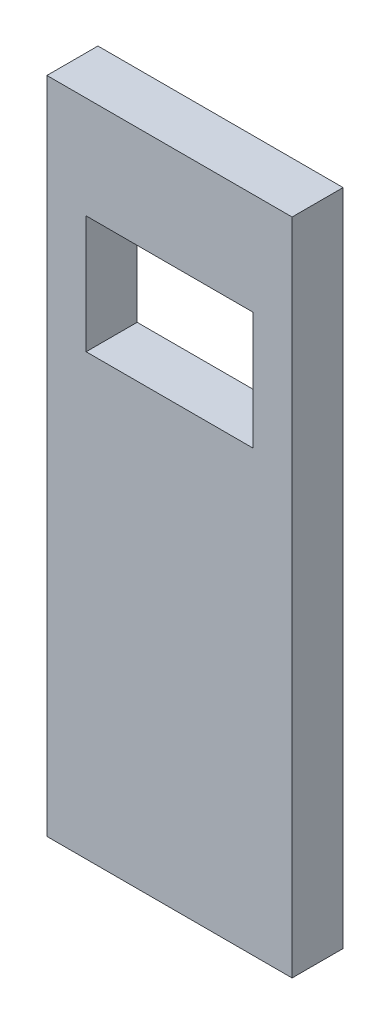
SolidWorks part; units mm, degrees
ref_plane "Front Plane" through (0, 0, 0) normal (0, 0, 1) x (1, 0, 0)
ref_plane "Top Plane" through (0, 0, 0) normal (0, 1, 0) x (1, 0, 0)
ref_plane "Right Plane" through (0, 0, 0) normal (1, 0, 0) x (0, 0, -1)
sketch "Sketch1" plane through (0, 0, 0) normal (0, 0, 1) x (1, 0, 0)
  line L0 (0, 67.2) -> (0, 44.8)
  line L1 (0, 67.2) -> (25, 67.2)
  line L2 (0, 44.8) -> (0, 39.6)
  line L3 (25, 0) -> (0, 0)
  line L4 (4, 56.8) -> (21, 56.8)
  line L5 (4, 44.8) -> (21, 44.8)
  line L6 (4, 56.8) -> (4, 44.8)
  line L7 (21, 56.8) -> (21, 44.8)
  line L8 (0, 44.8) -> (25, 44.8) construction
  line L9 (0, 39.6) -> (25, 39.6) construction
  line L10 (0, 39.6) -> (0, 27.6)
  line L11 (0, 27.6) -> (0, 22.4)
  line L12 (25, 44.8) -> (25, 39.6)
  line L13 (25, 67.2) -> (25, 44.8)
  line L14 (0, 22.4) -> (0, 0)
  line L15 (25, 39.6) -> (25, 27.6)
  line L16 (25, 27.6) -> (25, 22.4)
  line L17 (25, 22.4) -> (25, 0)
  line L18 (0, 27.6) -> (25, 27.6) construction
  line L19 (25, 22.4) -> (0, 22.4) construction
  line L20 (12.5, -0.0005) -> (12.5, 4.0956) construction
  point P18 (12.5, 44.8)
  point P20 (12.5, 56.8)
  point P21 (12.5, 67.2)
  dimension "D1" = 10.4
  dimension "D2" = 12
  dimension "D3" = 5.2
  dimension "D4" = 25
  dimension "D5" = 12
  dimension "D6" = 17
  dimension "D7" = 22.4
extrude "Boss-Extrude1" add sketch "Sketch1" along normal mid plane 5.2
